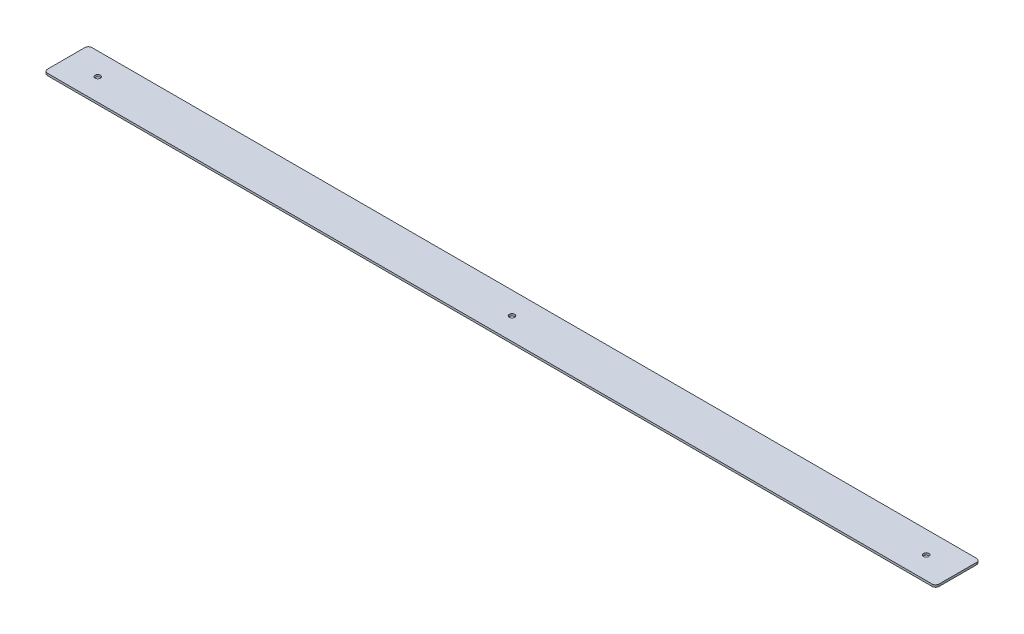
SolidWorks part; units mm, degrees
ref_plane "Front Plane" through (0, 0, 0) normal (0, 0, 1) x (1, 0, 0)
ref_plane "Top Plane" through (0, 0, 0) normal (0, 1, 0) x (1, 0, 0)
ref_plane "Right Plane" through (0, 0, 0) normal (1, 0, 0) x (0, 0, -1)
sketch "Sketch1" plane through (0, 0, 0) normal (0, 1, 0) x (1, 0, 0)
  line L1 (-318.2832, -15.875) -> (318.2832, -15.875)
  line L2 (-318.2832, -15.875) -> (-318.2832, 15.875)
  line L3 (-318.2832, 15.875) -> (318.2832, 15.875)
  line L4 (318.2832, -15.875) -> (318.2832, 15.875)
  line L5 (-318.2832, -15.875) -> (318.2832, 15.875) construction
  line L6 (-318.2832, 15.875) -> (318.2832, -15.875) construction
  point P0 (0, 0)
  dimension "D1" = 31.75
  dimension "D2" = 636.5663
extrude "Boss-Extrude1" add sketch "Sketch1" along normal blind 1.524
sketch "Sketch2" plane through (0, 1.524, 0) normal (0, 1, 0) x (1, 0, 0)
  line L0 (-318.2832, 15.875) -> (318.2832, -15.875) construction
  line L1 (-295.6983, 0) -> (295.6983, 0) construction
  circle A0 centre (-295.6983, 0) radius 1.905
  circle A1 centre (295.6983, 0) radius 1.905
  circle A2 centre (0, 0) radius 1.905
  point P8 (0, 0)
  dimension "D2" = 3.81
  dimension "D1" = 591.3967
extrude "Cut-Extrude1" cut sketch "Sketch2" against normal through all
fillet "Fillet1" radius 2.54 4 edges at (318.2832, 0.762, 15.875) (318.2832, 0.762, -15.875) (-318.2832, 0.762, 15.875) (-318.2832, 0.762, -15.875)
